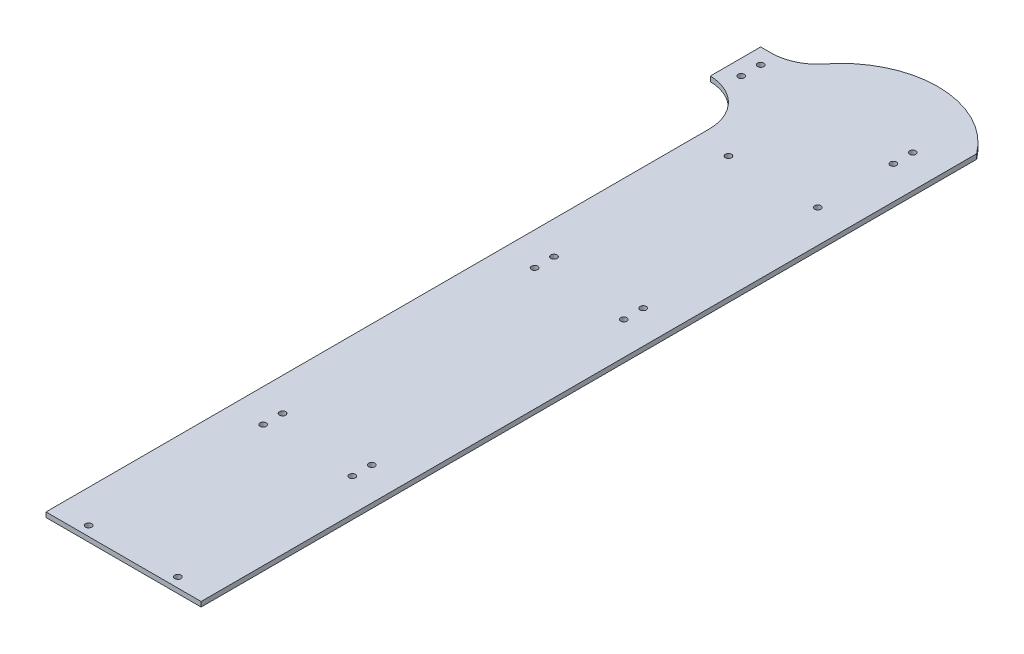
SolidWorks part; units mm, degrees
ref_plane "Front Plane" through (0, 0, 0) normal (0, 0, 1) x (1, 0, 0)
ref_plane "Top Plane" through (0, 0, 0) normal (0, 1, 0) x (1, 0, 0)
ref_plane "Right Plane" through (0, 0, 0) normal (1, 0, 0) x (0, 0, -1)
sketch "Sketch1" plane through (0, 0, 0) normal (0, 1, 0) x (1, 0, 0)
  line L2 (0, 0) -> (0, -508)
  line L3 (0, -508) -> (101.6, -508)
  line L4 (101.6, 0) -> (101.6, -508)
  arc A0 (0, 0) -> (101.6, 0) centre (50.8, -38.1) cw
  dimension "D3" = 63.5
  dimension "D1" = 508
  dimension "D2" = 101.6
extrude "Boss-Extrude1" add sketch "Sketch1" along normal blind 3.175
sketch "Sketch2" plane through (0, 0, 0) normal (0, -1, 0) x (1, 0, 0)
  line L0 (21.59, 82.55) -> (80.01, 82.55) construction
  line L1 (0, 508) -> (101.6, 508) construction
  circle A0 centre (21.59, 501.65) radius 2.032
  circle A1 centre (80.01, 501.65) radius 2.032
  circle A2 centre (21.59, 82.55) radius 2.032
  circle A3 centre (80.01, 82.55) radius 2.032
  arc A4 (0, 0) -> (101.6, 0) centre (50.8, 38.1) ccw construction
  circle A5 centre (21.59, 209.55) radius 2.032
  circle A6 centre (80.01, 209.55) radius 2.032
  circle A7 centre (21.59, 196.85) radius 2.032
  circle A8 centre (80.01, 196.85) radius 2.032
  circle A9 centre (21.59, 374.65) radius 2.032
  circle A10 centre (80.01, 374.65) radius 2.032
  circle A11 centre (21.59, 387.35) radius 2.032
  circle A12 centre (80.01, 387.35) radius 2.032
  point P11 (50.8, -25.4)
  point P12 (50.8, 82.55)
  dimension "D1" = 4.064
  dimension "D2" = 58.42
  dimension "D3" = 6.35
  dimension "D4" = 419.1
  dimension "D5" = 114.3
  dimension "D6" = 177.8
  dimension "D7" = 12.7
  dimension "D8" = 12.7
extrude "Cut-Extrude1" cut sketch "Sketch2" against normal through all
sketch "Sketch6" plane through (0, 3.175, 0) normal (0, 1, 0) x (1, 0, 0)
sketch "Sketch10" plane through (0, 0, 0) normal (0, -1, 0) x (-1, 0, 0)
  line L2 (0, 0) -> (76.2, 0)
  line L3 (0, 0) -> (0, -152.4)
  line L4 (0, -152.4) -> (76.2, -152.4)
  line L5 (76.2, 0) -> (76.2, -152.4)
  dimension "D1" = 152.4
  dimension "D2" = 76.2
extrude "Boss-Extrude6" add sketch "Sketch10" against normal up to surface (3.175 mm away) up to face at (80.01, 3.175, 207.518)
sketch "Sketch8" plane through (0, 0, 0) normal (0, -1, 0) x (-1, 0, 0)
  line L0 (-80.01, -80.518) -> (-80.01, -50.8583) construction
  line L1 (0, -508) -> (-101.6, -508) construction
  circle A0 centre (19.558, -33.0073) radius 2.032
  circle A1 centre (-80.01, -33.0073) radius 2.032
  circle A2 centre (19.558, -20.3073) radius 2.032
  circle A3 centre (-80.01, -20.3073) radius 2.032
  circle A4 centre (-80.01, -82.55) radius 2.032 construction
  dimension "D1" = 4.064
  dimension "D2" = 99.568
  dimension "D3" = 12.7
  dimension "D4" = 474.9927
extrude "Cut-Extrude4" cut sketch "Sketch8" against normal through all
sketch "Sketch16" plane through (0, 0, 0) normal (0, -1, 0) x (-1, 0, 0)
  line L0 (76.2, -152.4) -> (76.2, 0) construction
  line L1 (0, -152.4) -> (76.2, -152.4)
  line L2 (0, -152.4) -> (0, -43.1673)
  line L3 (0, -43.1673) -> (76.2, -43.1673)
  line L4 (76.2, -152.4) -> (76.2, -43.1673)
  line L6 (0, 0) -> (76.2, 0)
  line L7 (0, 0) -> (0, -10.1473)
  line L8 (0, -10.1473) -> (76.2, -10.1473)
  line L9 (76.2, 0) -> (76.2, -10.1473)
  line L10 (76.2, -43.1673) -> (29.718, -43.1673)
  line L11 (76.2, -43.1673) -> (76.2, -10.1473)
  line L12 (76.2, -10.1473) -> (29.718, -10.1473)
  line L13 (29.718, -43.1673) -> (29.718, -10.1473)
  circle A0 centre (19.558, -33.0073) radius 2.032 construction
  circle A1 centre (19.558, -20.3073) radius 2.032 construction
  line M27 (0, -152.4) -> (76.2, -152.4)
  line M28 (76.2, -152.4) -> (76.2, 0)
  line M29 (76.2, 0) -> (0, 0)
  dimension "D1" = 10.16
  dimension "D2" = 10.16
  dimension "D3" = 10.16
extrude "Cut-Extrude5" cut sketch "Sketch16" against normal through all contours L3 L2 M27 M28 | L13 L3 L8 M28 | L7 L8 M28 M29 region at (-38.1, 0, 97.7836) region at (-52.959, 0, 26.6573) region at (-38.1, 0, 5.0736)
sketch "Sketch17" plane through (0, 0, 0) normal (0, -1, 0) x (1, 0, 0)
  line L0 (101.6, 508) -> (101.6, 0) construction
  line L1 (16.9061, 42.1497) -> (27.1204, 42.1497)
  line L2 (16.9061, 42.1497) -> (16.9061, 32.6649)
  line L3 (16.9061, 32.6649) -> (27.1204, 32.6649)
  line L4 (27.1204, 42.1497) -> (27.1204, 32.6649)
  line L5 (75.0662, 40.806) -> (85.3535, 40.806)
  line L6 (75.0662, 40.806) -> (75.0662, 35.2727)
  line L7 (75.0662, 35.2727) -> (85.3535, 35.2727)
  line L8 (85.3535, 40.806) -> (85.3535, 35.2727)
  line L9 (0, 10.1473) -> (-29.718, 10.1473) construction
  line L10 (0, 43.1673) -> (0, 508) construction
  dimension "D1" = 5.5333
  dimension "D2" = 10.2873
  dimension "D3" = 16.2465
  dimension "D4" = 25.1254
  dimension "D5" = 10.2143
  dimension "D6" = 9.4847
  dimension "D7" = 16.9061
  dimension "D8" = 22.5176
extrude "Boss-Extrude11" add sketch "Sketch17" against normal up to surface (3.175 mm away) up to face at (80.01, 3.175, 30.9753)
fillet "Fillet1" radius 30.48 2 edges at (0, 1.5875, 43.1673) (0, 1.5875, 10.1473)
